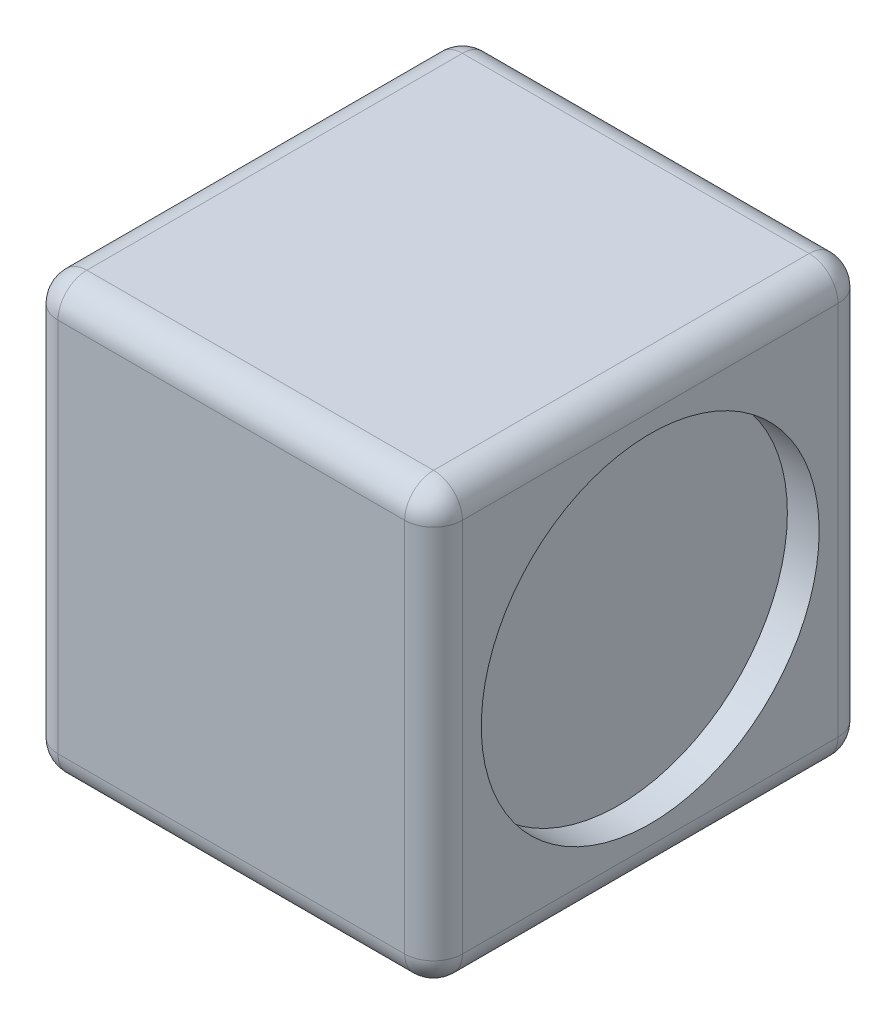
SolidWorks part; units mm, degrees
ref_plane "Front Plane" through (0, 0, 0) normal (0, 0, 1) x (1, 0, 0)
ref_plane "Top Plane" through (0, 0, 0) normal (0, 1, 0) x (1, 0, 0)
ref_plane "Right Plane" through (0, 0, 0) normal (1, 0, 0) x (0, 0, -1)
sketch "Sketch1" plane through (0, 0, 0) normal (0, 1, 0) x (1, 0, 0)
  line L1 (-17.78, 19.05) -> (17.78, 19.05)
  line L2 (-17.78, 19.05) -> (-17.78, -19.05)
  line L3 (-17.78, -19.05) -> (17.78, -19.05)
  line L4 (17.78, 19.05) -> (17.78, -19.05)
  line L5 (-17.78, 19.05) -> (17.78, -19.05) construction
  line L6 (-17.78, -19.05) -> (17.78, 19.05) construction
  point P0 (0, 0)
  dimension "D1" = 35.56
  dimension "D2" = 38.1
extrude "Boss-Extrude1" add sketch "Sketch1" along normal blind 38.1
fillet "Fillet1" radius 2.54 12 edges at (17.78, 19.05, -19.05) (-17.78, 19.05, -19.05) (-17.78, 19.05, 19.05) (17.78, 19.05, 19.05) (0, 38.1, 19.05) (-17.78, 38.1, 0) (0, 38.1, -19.05) (17.78, 38.1, 0) (0, 0, -19.05) (-17.78, 0, 0) (0, 0, 19.05) (17.78, 0, 0)
sketch "Sketch2" plane through (0, 38.1, 0) normal (0, 1, 0) x (1, 0, 0)
sketch "Sketch4" plane through (17.78, 0, 0) normal (1, 0, 0) x (0, 0, -1)
  circle A0 centre (0, 19.05) radius 14.8536
extrude "Cut-Extrude2" cut sketch "Sketch4" against normal blind 2.794
sketch "Sketch5" plane through (0, 0, 0) normal (0, -1, 0) x (1, 0, 0)
  line L9 (-8.89, 0) -> (-8.89, -6.35)
  line L10 (-8.89, 6.35) -> (-2.54, 6.35)
  line L11 (-8.89, 6.35) -> (-8.89, -6.35)
  line L12 (-8.89, -6.35) -> (-2.54, -6.35)
  line L13 (-2.54, 6.35) -> (-2.54, -6.35)
  dimension "D2" = 6.35
  dimension "D3" = 6.35
  dimension "D4" = 6.35
extrude "Boss-Extrude2" add sketch "Sketch5" along normal blind 1.27 contours L11 L10 L13 L12
ref_axis "Axis1" through (14.986, 19.05, 0) along (1, 0, 0)
